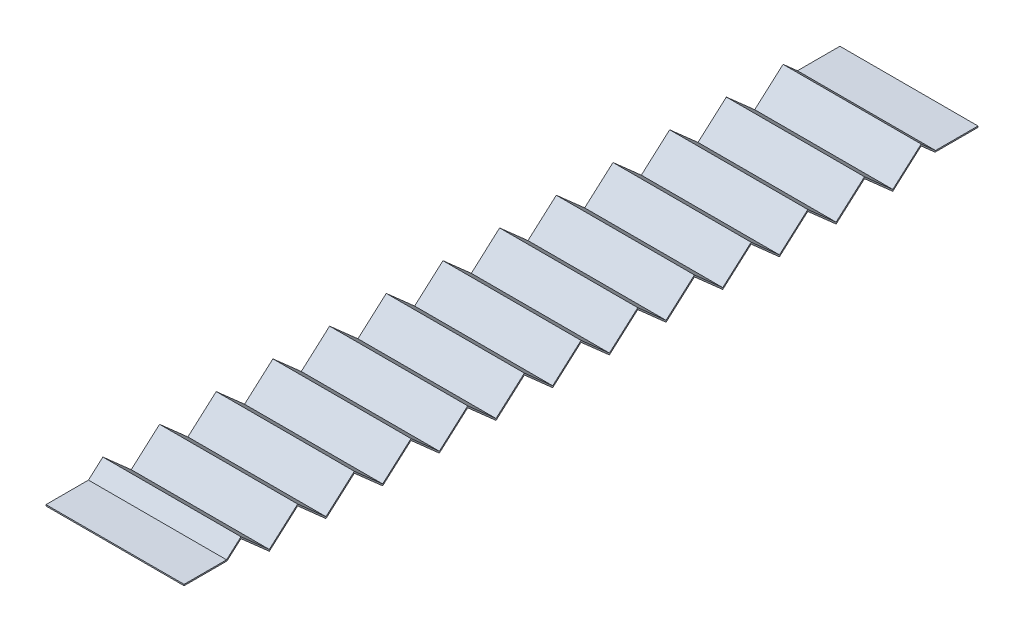
SolidWorks part; units mm, degrees
ref_plane "Front Plane" through (0, 0, 0) normal (0, 0, 1) x (1, 0, 0)
ref_plane "Top Plane" through (0, 0, 0) normal (0, 1, 0) x (1, 0, 0)
ref_plane "Right Plane" through (0, 0, 0) normal (1, 0, 0) x (0, 0, -1)
sketch "Sketch2" plane through (0, 0, 0) normal (0, 0, 1) x (1, 0, 0)
  line L1 (-27.5, 10) -> (27.5, 10)
  line L2 (-27.5, 10) -> (-27.5, 0)
  line L3 (-27.5, 0) -> (27.5, 0)
  line L4 (27.5, 10) -> (27.5, 0)
  point P4 (0, 0)
  dimension "D1" = 10
  dimension "D2" = 55
sketch "Sketch3" plane through (0, 0, 0) normal (1, 0, 0) x (0, 0, -1)
  line L0 (0, 10) -> (316.1578, 10) construction
  line L1 (0, 0) -> (316.1578, 0) construction
  line L3 (17, 5) -> (22.6432, 10)
  line L4 (22.6432, 10) -> (33.9295, 0)
  line L5 (33.9295, 0) -> (45.2158, 10)
  line L6 (45.2158, 10) -> (56.5021, 0)
  line L7 (56.5021, 0) -> (67.7884, 10)
  line L8 (67.7884, 10) -> (79.0747, 0)
  line L9 (79.0747, 0) -> (90.361, 10)
  line L10 (90.361, 10) -> (101.6473, 0)
  line L11 (101.6473, 0) -> (112.9336, 10)
  line L12 (112.9336, 10) -> (124.2199, 0)
  line L13 (124.2199, 0) -> (135.5063, 10)
  line L14 (135.5063, 10) -> (146.7926, 0)
  line L15 (146.7926, 0) -> (158.0789, 10)
  line L16 (158.0789, 10) -> (169.3652, 0)
  line L17 (169.3652, 0) -> (180.6515, 10)
  line L18 (180.6515, 10) -> (191.9378, 0)
  line L19 (0, 10) -> (0, 0) construction
  line L20 (191.9378, 0) -> (203.2241, 10)
  line L21 (203.2241, 10) -> (214.5104, 0)
  line L22 (214.5104, 0) -> (225.7967, 10)
  line L23 (225.7967, 10) -> (237.083, 0)
  line L24 (237.083, 0) -> (248.3694, 10)
  line L25 (248.3694, 10) -> (259.6557, 0)
  line L26 (259.6557, 0) -> (270.942, 10)
  line L27 (270.942, 10) -> (282.2283, 0)
  line L28 (282.2283, 0) -> (293.5146, 10)
  line L29 (293.5146, 10) -> (299.1578, 5)
  line L30 (316.1578, 10) -> (316.1578, 0) construction
  line L31 (17, 5) -> (0, 5)
  line L32 (299.1578, 5) -> (316.1578, 5)
  line L34 (316.1578, 4.75) -> (316.1578, 22.75) construction
  dimension "D2" = 17
  dimension "D1" = 10
  dimension "D3" = 17
extrude "Extrude-Thin1" add sketch "Sketch3" against normal mid plane 55 thin thin type mid plane wall 0.5
